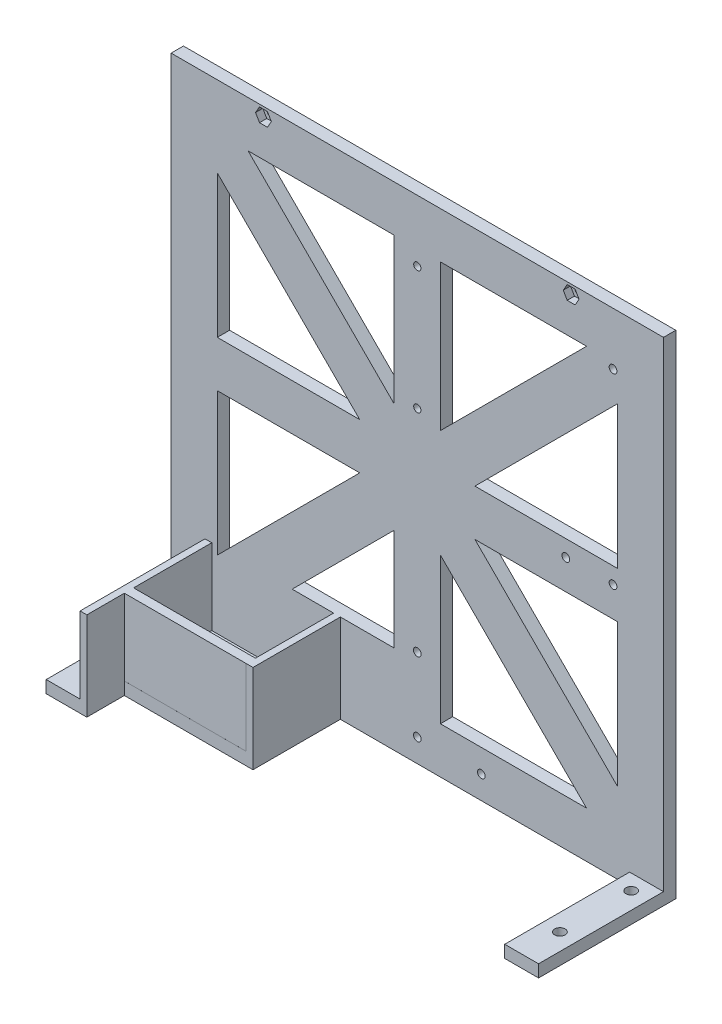
SolidWorks part; units mm, degrees
ref_plane "Front" through (0, 0, 0) normal (0, 0, 1) x (1, 0, 0)
ref_plane "Top" through (0, 0, 0) normal (0, 1, 0) x (1, 0, 0)
ref_plane "Right" through (0, 0, 0) normal (1, 0, 0) x (0, 0, -1)
sketch "Sketch1" plane through (0, 0, 0) normal (0, 0, 1) x (1, 0, 0)
  line L1 (-101.6, 101.6) -> (101.6, 101.6)
  line L2 (-101.6, 101.6) -> (-101.6, -101.6)
  line L3 (-101.6, -101.6) -> (101.6, -101.6)
  line L4 (101.6, 101.6) -> (101.6, -101.6)
  line L5 (-101.6, 101.6) -> (101.6, -101.6) construction
  line L6 (-101.6, -101.6) -> (101.6, 101.6) construction
  line L7 (0, -55) -> (0, 55) construction
  line L10 (-9.525, -22.8914) -> (-9.525, -65.024)
  line L17 (9.525, 22.225) -> (69.85, 82.55)
  line L18 (9.525, 82.55) -> (9.525, 22.225)
  line L19 (69.85, 82.55) -> (9.525, 82.55)
  line L23 (23.7658, 9.525) -> (82.55, 9.525)
  line L24 (23.7658, -9.525) -> (82.55, -9.525)
  line L25 (23.7658, 9.525) -> (82.55, 68.3092)
  line L26 (23.7658, -9.525) -> (82.55, -68.3092)
  line L27 (82.55, 9.525) -> (82.55, 68.3092)
  line L28 (82.55, -9.525) -> (82.55, -68.3092)
  line L29 (9.525, -22.225) -> (69.85, -82.55)
  line L30 (69.85, -82.55) -> (9.525, -82.55)
  line L31 (9.525, -82.55) -> (9.525, -22.225)
  line L32 (0, -101.6) -> (0, 101.6) construction
  line L36 (-82.55, -9.525) -> (-82.55, -68.3092)
  line L37 (-82.55, 9.525) -> (-82.55, 68.3092)
  line L38 (-23.7658, -9.525) -> (-82.55, -68.3092)
  line L39 (-23.7658, 9.525) -> (-82.55, 68.3092)
  line L40 (-23.7658, -9.525) -> (-82.55, -9.525)
  line L41 (-23.7658, 9.525) -> (-82.55, 9.525)
  line L42 (-69.85, 82.55) -> (-9.525, 82.55)
  line L43 (-9.525, 82.55) -> (-9.525, 22.225)
  line L44 (-9.525, 22.225) -> (-69.85, 82.55)
  line L45 (-9.525, -65.024) -> (-51.6576, -65.024)
  line L46 (-51.6576, -65.024) -> (-9.525, -22.8914)
  circle A0 centre (0, 76.2) radius 1.5
  circle A2 centre (0, 25.4) radius 1.5
  circle A3 centre (-63.5, 97.79) radius 1.5
  circle A4 centre (63.5, 97.79) radius 1.5
  point P0 (0, 0)
  dimension "D3" = 3
  dimension "D4" = 50.8
  dimension "D6" = 19.05
  dimension "D7" = 3
  dimension "D9" = 63.5
  dimension "D1" = 203.2
  dimension "D2" = 203.2
  dimension "D5" = 25.4
  dimension "D8" = 3.81
  dimension "D10" = 19.05
  dimension "D11" = 19.05
  dimension "D12" = 19.05
  dimension "D13" = 19.05
  dimension "D14" = 19.05
  dimension "D15" = 9.525
  dimension "D16" = 36.576
  dimension "D17" = 31.75
extrude "Boss-Extrude1" add sketch "Sketch1" along normal blind 5.08 contours L4 L1 L2 L3 A2 A0 L19 L17 L18 region at (-1.1784, -2.5163, 0)
sketch "Sketch2" plane through (0, 0, 5.08) normal (0, 0, 1) x (1, 0, 0)
  line L0 (-101.6, -101.6) -> (101.6, -101.6) construction
  line L2 (-101.6, -101.6) -> (-101.6, -96.52)
  line L5 (-9.525, -65.024) -> (-51.6576, -65.024) construction
  line L13 (-101.6, -101.6) -> (-31.75, -101.6)
  line L17 (-87.63, -65.024) -> (-84.836, -65.024)
  line L18 (-84.836, -96.4094) -> (-84.836, -65.024)
  line L23 (-84.836, -96.4094) -> (-34.544, -96.4094)
  line L24 (-101.6, -96.52) -> (-87.63, -96.52)
  line L25 (-87.63, -96.52) -> (-87.63, -65.024)
  line L28 (-34.544, -96.4094) -> (-34.544, -65.024)
  line L29 (-34.544, -65.024) -> (-31.75, -65.024)
  line L30 (-31.75, -65.024) -> (-31.75, -101.6)
  line L31 (101.6, -101.6) -> (87.63, -101.6)
  line L32 (101.6, -101.6) -> (101.6, -96.52)
  line L33 (101.6, -96.52) -> (87.63, -96.52)
  line L34 (87.63, -101.6) -> (87.63, -96.52)
  line M7 (101.6, -101.6) -> (101.6, 101.6)
  line M9 (-101.6, 101.6) -> (-101.6, -101.6)
  line M10 (-101.6, -101.6) -> (101.6, -101.6)
  dimension "D1" = 5.08
  dimension "D2" = 50.292
  dimension "D4" = 13.97
  dimension "D5" = 2.794
  dimension "D6" = 2.794
  dimension "D8" = 31.3854
extrude "Boss-Extrude2" add sketch "Sketch2" along normal blind 51.562 contours L23 L18 L17 L25 L24 M10 M9 | L34 L33 M10 M7 region at (94.615, -99.06, 5.08) region at (-100.8115, -99.06, 5.08)
sketch "Sketch3" plane through (0, -96.52, 0) normal (0, 1, 0) x (1, 0, 0)
  line L0 (-101.6, 0) -> (101.6, 0) construction
  line L2 (-87.63, -56.642) -> (-87.63, -5.08) construction
  line L4 (0, -2.794) -> (0, 2.794) construction
  line L5 (-101.6, -56.642) -> (-101.6, -5.08) construction
  circle A0 centre (-94.615, -11.43) radius 2.159
  circle A1 centre (94.615, -11.43) radius 2.159
  circle A2 centre (-94.615, -40.84) radius 2.159
  circle A3 centre (94.615, -40.84) radius 2.159
  dimension "D1" = 4.318
  dimension "D4" = 29.41
  dimension "D5" = 4.318
  dimension "D6" = 4.318
  dimension "D7" = 6.985
  dimension "D2" = 11.43
  dimension "D8" = 29.41
  dimension "D3" = 6.985
extrude "Cut-Extrude1" cut sketch "Sketch3" against normal up to next contours A0 | A1 | A3 | A2 | A2 | A3 region at (-94.615, -96.52, 11.43) region at (94.615, -96.52, 11.43) region at (-94.615, -96.52, 40.84) region at (94.615, -96.52, 40.84)
sketch "Sketch7" plane through (0, 0, 5.08) normal (0, 0, 1) x (1, 0, 0)
  line L1 (69.85, -82.55) -> (9.525, -82.55) construction
  circle A0 centre (0, -92.075) radius 1.5875
  circle A1 centre (0, -61.722) radius 1.5875
  circle A3 centre (26.416, -92.075) radius 1.5875
  dimension "D1" = 3.175
  dimension "D3" = 26.416
  dimension "D5" = 9.525
extrude "Cut-Extrude2" cut sketch "Sketch7" against normal up to next
sketch "Sketch11" plane through (0, 0, 5.08) normal (0, 0, 1) x (1, 0, 0)
  line L0 (0, -31.1531) -> (0, 31.1531) construction
  line L1 (-61.869, 94.965) -> (-60.238, 97.79)
  line L2 (-60.238, 97.79) -> (-61.869, 100.615)
  line L3 (-61.869, 100.615) -> (-65.131, 100.615)
  line L4 (-65.131, 100.615) -> (-66.762, 97.79)
  line L5 (-66.762, 97.79) -> (-65.131, 94.965)
  line L6 (-65.131, 94.965) -> (-61.869, 94.965)
  line L7 (65.131, 94.965) -> (61.869, 94.965)
  line L8 (66.762, 97.79) -> (65.131, 94.965)
  line L9 (65.131, 100.615) -> (66.762, 97.79)
  line L10 (61.869, 100.615) -> (65.131, 100.615)
  line L11 (60.238, 97.79) -> (61.869, 100.615)
  line L12 (61.869, 94.965) -> (60.238, 97.79)
  circle A0 centre (-63.5, 97.79) radius 1.5 construction
  circle A1 centre (-63.5, 97.79) radius 1.5
  circle A2 centre (-63.5, 97.79) radius 2.825 construction
  circle A3 centre (63.5, 97.79) radius 2.825 construction
  circle A4 centre (63.5, 97.79) radius 1.5
  circle M36 centre (-63.5, 97.79) radius 1.5
  circle M37 centre (63.5, 97.79) radius 1.5
  dimension "D1" = 5.65
extrude "Cut-Extrude4" cut sketch "Sketch11" against normal blind 3 contours L5 L6 L1 L2 L3 L4 M36 | L12 L7 L8 L9 L10 L11 M37 region at (-63.5, 95.0513, 5.08) region at (63.5, 95.0513, 5.08)
sketch "Sketch12" plane through (-34.544, 0, 0) normal (-1, 0, 0) x (0, 0, 1)
  line L0 (56.642, -96.52) -> (5.08, -96.52) construction
  line L1 (41.148, -96.52) -> (37.338, -96.52)
  line L2 (41.148, -96.52) -> (41.148, -65.024)
  line L3 (41.148, -65.024) -> (37.338, -65.024)
  line L4 (37.338, -96.52) -> (37.338, -65.024)
  line L5 (56.642, -65.024) -> (5.08, -65.024) construction
  line L6 (5.08, 101.6) -> (5.08, -96.52) construction
  dimension "D1" = 3.81
  dimension "D2" = 32.258
extrude "Boss-Extrude3" add sketch "Sketch12" along normal up to next
sketch "Sketch14" plane through (-31.75, 0, 0) normal (1, 0, 0) x (0, 0, -1)
  line L0 (-56.642, -65.024) -> (-5.08, -65.024) construction
  line L1 (-56.642, -101.6) -> (-41.152, -101.6)
  line L2 (-56.642, -101.6) -> (-56.642, -65.024)
  line L3 (-56.642, -65.024) -> (-41.152, -65.024)
  line L4 (-41.152, -101.6) -> (-41.152, -65.024)
  dimension "D1" = 15.49
extrude "Cut-Extrude5" cut sketch "Sketch14" against normal up to surface (53.086 mm away) up to face at (-84.836, -80.7167, 48.895)
sketch "Sketch15" plane through (0, 0, 5.08) normal (0, 0, 1) x (1, 0, 0)
  line L0 (61.2852, -38.9377) -> (80.7852, -38.9377) construction
  line L1 (61.2852, 37.854) -> (80.7852, 37.854) construction
  line L2 (61.2852, 37.854) -> (61.2852, 79.854) construction
  line L3 (61.2852, 79.854) -> (80.7852, 79.854) construction
  line L4 (80.7852, 37.854) -> (80.7852, 79.854) construction
  line L5 (61.2852, -38.9377) -> (61.2852, 2.7864) construction
  line L6 (61.2852, 2.7864) -> (80.7852, 2.7864) construction
  line L7 (80.7852, -38.9377) -> (80.7852, 2.7864) construction
  circle A0 centre (61.2852, 79.854) radius 1.6
  circle A1 centre (80.7852, 79.854) radius 1.6
  circle A2 centre (80.7852, 37.854) radius 1.6
  circle A3 centre (61.2852, 37.854) radius 1.6
  circle A4 centre (61.2852, 2.7864) radius 1.6
  circle A5 centre (80.7852, 2.7864) radius 1.6
  circle A6 centre (80.7852, -38.9377) radius 1.6
  circle A7 centre (61.2852, -38.9377) radius 1.6
  dimension "D1" = 19.5
  dimension "D2" = 42
  dimension "D3" = 3.2
  dimension "D4" = 3.2
  dimension "D5" = 3.2
  dimension "D6" = 3.2
  dimension "D8" = 3.2
  dimension "D9" = 3.2
  dimension "D10" = 3.2
  dimension "D7" = 19.5
  dimension "D11" = 41.7241
extrude "Cut-Extrude6" cut sketch "Sketch15" against normal blind 10
